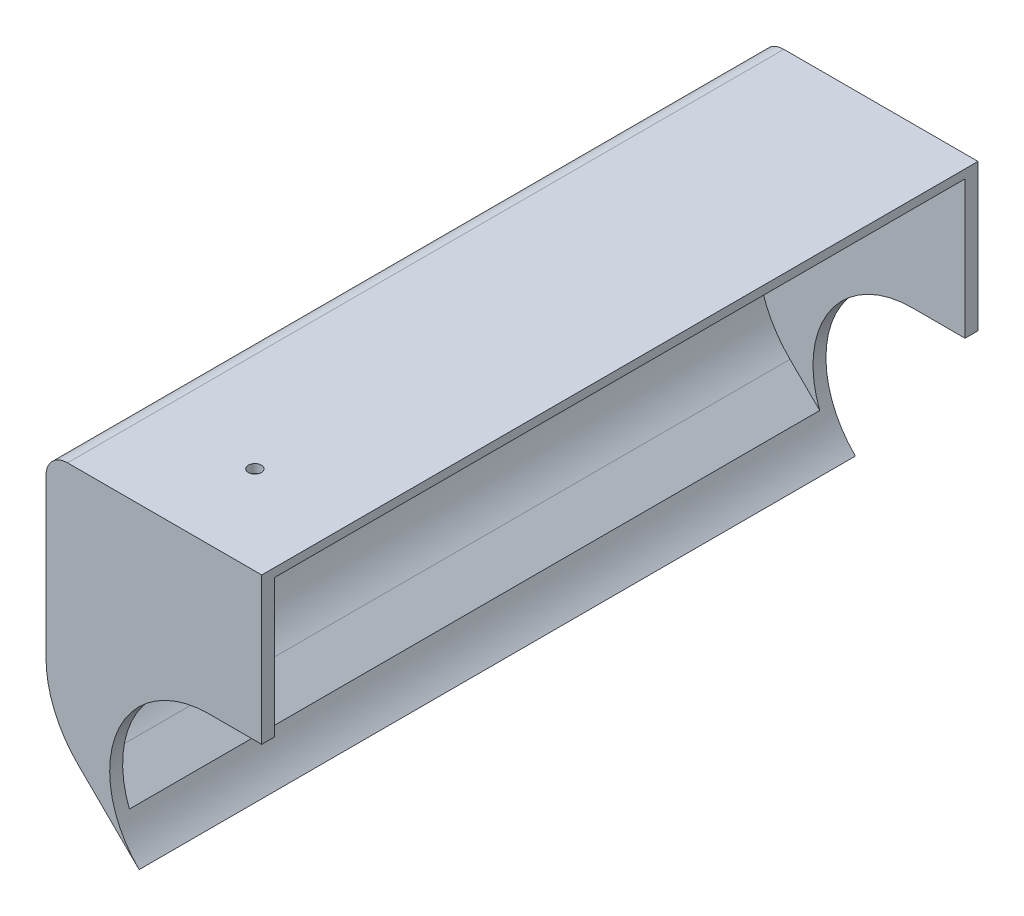
SolidWorks part; units mm, degrees
ref_plane "Front Plane" through (0, 0, 0) normal (0, 0, 1) x (1, 0, 0)
ref_plane "Top Plane" through (0, 0, 0) normal (0, 1, 0) x (1, 0, 0)
ref_plane "Right Plane" through (0, 0, 0) normal (1, 0, 0) x (0, 0, -1)
sketch "Sketch1" plane through (0, 0, 0) normal (0, 0, 1) x (1, 0, 0)
  line L0 (-176.4226, 3.6462) -> (-198.0073, 24.9918)
  line L1 (-198.0073, 24.9918) -> (-198.0073, 77)
  line L2 (-198.0073, 77) -> (-148.0073, 77)
  line L4 (-160.25, 43) -> (-148.0073, 43)
  line L6 (-148.0073, 43) -> (-148.0073, 77)
  arc A1 (-160.25, 43) -> (-176.4226, 3.6462) centre (-160.25, 20) ccw
extrude "Boss-Extrude1" add sketch "Sketch1" against normal blind 3
sketch "Sketch2" plane through (0, 0, -166) normal (0, 0, -1) x (-1, 0, 0)
  line L5 (198.0073, 24.9918) -> (198.0073, 77)
  line L6 (198.0073, 77) -> (148.0073, 77)
  line L7 (148.0073, 77) -> (148.0073, 43)
  line L8 (148.0073, 43) -> (160.25, 43)
  line L9 (176.4226, 3.6462) -> (198.0073, 24.9918)
  line L10 (198.0073, 24.9918) -> (198.0073, 77)
  line L11 (198.0073, 77) -> (148.0073, 77)
  line L12 (148.0073, 77) -> (148.0073, 43)
  line L13 (148.0073, 43) -> (160.25, 43)
  line L14 (176.4226, 3.6462) -> (198.0073, 24.9918)
  arc A1 (176.4226, 3.6462) -> (160.25, 43) centre (160.25, 20) ccw
  arc A2 (176.4226, 3.6462) -> (160.25, 43) centre (160.25, 20) ccw
  dimension "D1" = 0
extrude "Boss-Extrude2" add sketch "Sketch2" against normal blind 3 separate body
sketch "Sketch3" plane through (0, 0, -3) normal (0, 0, -1) x (-1, 0, 0)
  line L0 (181.6864, 11.6645) -> (196.0073, 25.8268)
  line L1 (196.0073, 25.8268) -> (196.0073, 75)
  line L2 (196.0073, 75) -> (148.0073, 75)
  line L3 (148.0073, 77) -> (148.0073, 75)
  line L4 (175.0163, 5.0683) -> (196.0073, 25.8268) construction
  line L5 (198.0073, 24.9918) -> (198.0073, 77)
  line L6 (198.0073, 77) -> (148.0073, 77)
  line L7 (148.0073, 77) -> (148.0073, 43)
  line L8 (148.0073, 43) -> (160.25, 43)
  line L9 (176.4226, 3.6462) -> (198.0073, 24.9918)
  line L10 (198.0073, 24.9918) -> (198.0073, 77)
  line L11 (198.0073, 77) -> (148.0073, 77)
  line L14 (176.4226, 3.6462) -> (198.0073, 24.9918)
  arc A0 (160.25, -3) -> (160.25, 43) centre (160.25, 20) ccw construction
  arc A1 (176.4226, 3.6462) -> (160.25, 43) centre (160.25, 20) ccw
  arc A3 (176.4226, 3.6462) -> (181.6864, 11.6645) centre (160.25, 20) ccw
  dimension "D1" = 0
  dimension "D2" = 2
extrude "Boss-Extrude3" add sketch "Sketch3" along normal up to surface (160 mm away) up to face at (-173.6482, 45.6762, -163)
fillet "Fillet1" radius 5 2 edges at (-198.0073, 77, -83) (-196.0073, 75, -83)
fillet "Fillet2" radius 25 2 edges at (-196.0073, 25.8268, -83) (-198.0073, 24.9918, -83)
sketch "Sketch4" plane through (-198.0073, 0, 0) normal (-1, 0, 0) x (0, 0, 1)
  line L0 (-166, 57) -> (0, 57) construction
  line L3 (-95, 57) -> (-71, 57) construction
  line L4 (-83, 57) -> (-83, 76.9624) construction
  circle A0 centre (-30, 47) radius 2.5
  circle A1 centre (-136, 47) radius 2.5
  circle A2 centre (-95, 57) radius 8.5
  circle A3 centre (-71, 57) radius 8.5
extrude "Cut-Extrude1" cut sketch "Sketch4" against normal blind 7
sketch "Sketch5" plane through (-196.0073, 0, 0) normal (1, 0, 0) x (0, 0, -1)
  line L4 (105.5, 67) -> (60.5, 67)
  line L5 (60.5, 67) -> (60.5, 47)
  line L6 (60.5, 47) -> (105.5, 47)
  line L7 (105.5, 47) -> (105.5, 67)
  line L8 (105.5, 67) -> (60.5, 67)
  line L9 (60.5, 67) -> (60.5, 47)
  line L10 (60.5, 47) -> (105.5, 47)
  line L11 (105.5, 47) -> (105.5, 67)
  circle A0 centre (71, 57) radius 8.5 construction
  circle A1 centre (71, 57) radius 8.5
  circle A2 centre (95, 57) radius 8.5 construction
  circle A3 centre (95, 57) radius 8.5
  dimension "D1" = 0
extrude "Boss-Extrude4" add sketch "Sketch5" along normal blind 8
sketch "Sketch6" plane through (-196.0073, 0, 0) normal (1, 0, 0) x (0, 0, -1)
  circle A0 centre (20.5, 60.4) radius 6
extrude "Cut-Extrude2" cut sketch "Sketch6" against normal up to surface (2 mm away) up to face at (-198.0073, 47, -27.5)
sketch "Sketch7" plane through (0, 77, 0) normal (0, 1, 0) x (1, 0, 0)
  circle A0 centre (-170.1073, 20.5) radius 1.5 construction
  circle A1 centre (-170.1073, 20.5) radius 1.5
extrude "Cut-Extrude3" cut sketch "Sketch7" against normal blind 3
